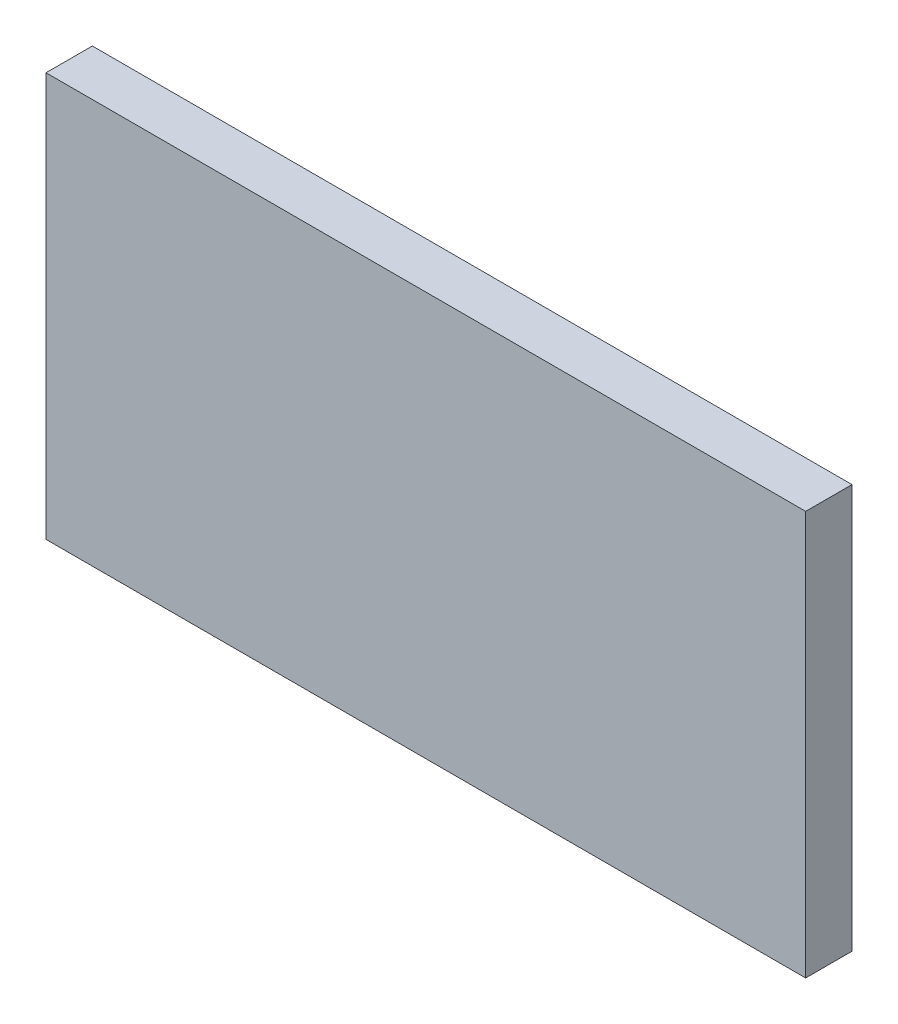
SolidWorks part; units mm, degrees
ref_plane "Plan de face" through (0, 0, 0) normal (0, 0, 1) x (1, 0, 0)
ref_plane "Plan de dessus" through (0, 0, 0) normal (0, 1, 0) x (1, 0, 0)
ref_plane "Plan de droite" through (0, 0, 0) normal (1, 0, 0) x (0, 0, -1)
sketch "Esquisse1" plane through (0, 0, 0) normal (0, 0, 1) x (1, 0, 0)
  line L0 (-125.25, 820.371) -> (125.25, 820.371) construction
  line L1 (-125, 822.371) -> (125, 822.371)
  line L2 (-125, 822.371) -> (-125, 955.371)
  line L3 (-125, 955.371) -> (125, 955.371)
  line L4 (125, 822.371) -> (125, 955.371)
  line L7 (-115.25, 955.371) -> (-125.25, 955.371) construction
  line L8 (0, 955.371) -> (0, 822.371) construction
  line L9 (0, -8.3875) -> (0, 8.3875) construction
  dimension "D1" = 2
  dimension "D2" = 250
extrude "Boss.-Extru.1" add sketch "Esquisse1" along normal blind 15.25
